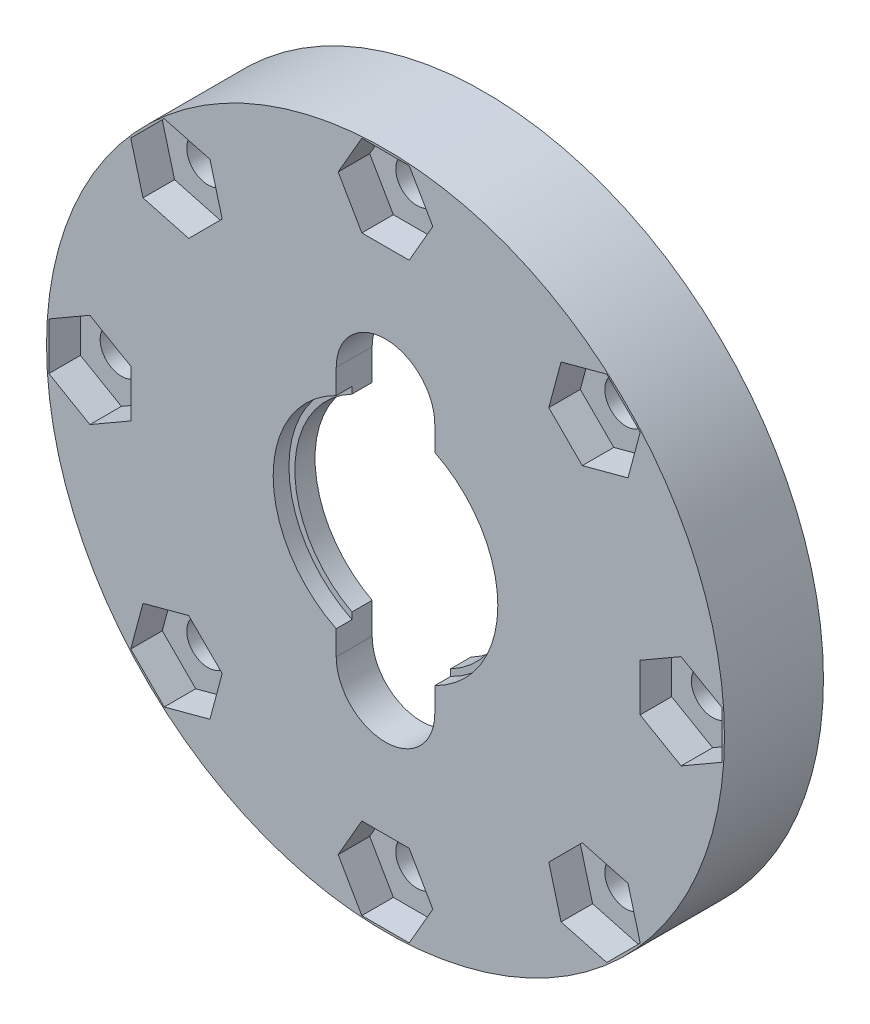
SolidWorks part; units mm, degrees
ref_plane "Front Plane" through (0, 0, 0) normal (0, 0, 1) x (1, 0, 0)
ref_plane "Top Plane" through (0, 0, 0) normal (0, 1, 0) x (1, 0, 0)
ref_plane "Right Plane" through (0, 0, 0) normal (1, 0, 0) x (0, 0, -1)
ref_axis "Z" through (0, 0, -6.594) along (0, 0, 1)
sketch "Sketch3" plane through (0, 0, 0) normal (0, 0, 1) x (1, 0, 0)
  line L0 (-3.125, -6.4031) -> (-3.125, -7.9497)
  line L1 (-3.125, -7.9497) -> (3.125, -7.9497)
  line L2 (3.125, -7.9497) -> (3.125, -6.4031)
  line L3 (3.125, 6.4031) -> (3.125, 7.9494)
  line L4 (3.125, 7.9494) -> (-3.125, 7.9494)
  line L5 (-3.125, 7.9494) -> (-3.125, 6.4031)
  line L132 (3.05, 6.3548) -> (3.05, 6.3561) construction
  line L133 (-3.05, 6.3561) -> (-3.05, 6.3548) construction
  line L134 (3.05, -6.3561) -> (3.05, -6.355) construction
  line L135 (-3.05, -6.355) -> (-3.05, -6.3561) construction
  line L198 (3.05, 6.3548) -> (3.05, 7.8744)
  line L199 (3.05, 7.8744) -> (-3.05, 7.8744)
  line L200 (-3.05, 7.8744) -> (-3.05, 6.3548)
  line L201 (-3.05, 6.3548) -> (-3.4914, 6.1247)
  line L202 (-3.4914, 6.1247) -> (-3.9416, 5.8451)
  line L203 (-3.9416, 5.8451) -> (-4.3696, 5.5325)
  line L204 (-4.3696, 5.5325) -> (-4.7729, 5.1886)
  line L205 (-4.7729, 5.1886) -> (-5.1492, 4.8154)
  line L206 (-5.1492, 4.8154) -> (-5.4964, 4.4149)
  line L207 (-5.4964, 4.4149) -> (-5.8125, 3.9896)
  line L208 (-5.8125, 3.9896) -> (-6.0958, 3.5417)
  line L209 (-6.0958, 3.5417) -> (-6.3446, 3.0737)
  line L210 (-6.3446, 3.0737) -> (-6.5576, 2.5884)
  line L211 (-6.5576, 2.5884) -> (-6.7335, 2.0885)
  line L212 (-6.7335, 2.0885) -> (-6.8714, 1.5768)
  line L213 (-6.8714, 1.5768) -> (-6.9705, 1.0561)
  line L214 (-6.9705, 1.0561) -> (-7.0301, 0.5295)
  line L215 (-7.0301, 0.5295) -> (-7.05, -0.0001)
  line L216 (-7.05, -0.0001) -> (-7.0301, -0.5297)
  line L217 (-7.0301, -0.5297) -> (-6.9705, -1.0563)
  line L218 (-6.9705, -1.0563) -> (-6.8714, -1.577)
  line L219 (-6.8714, -1.577) -> (-6.7335, -2.0887)
  line L220 (-6.7335, -2.0887) -> (-6.5576, -2.5887)
  line L221 (-6.5576, -2.5887) -> (-6.3446, -3.074)
  line L222 (-6.3446, -3.074) -> (-6.0958, -3.5419)
  line L223 (-6.0958, -3.5419) -> (-5.8125, -3.9898)
  line L224 (-5.8125, -3.9898) -> (-5.4964, -4.4152)
  line L225 (-5.4964, -4.4152) -> (-5.1492, -4.8156)
  line L226 (-5.1492, -4.8156) -> (-4.7729, -5.1888)
  line L227 (-4.7729, -5.1888) -> (-4.3696, -5.5327)
  line L228 (-4.3696, -5.5327) -> (-3.9416, -5.8453)
  line L229 (-3.9416, -5.8453) -> (-3.4914, -6.1249)
  line L230 (-3.4914, -6.1249) -> (-3.05, -6.355)
  line L231 (-3.05, -6.355) -> (-3.05, -7.8747)
  line L232 (-3.05, -7.8747) -> (3.05, -7.8747)
  line L233 (3.05, -7.8747) -> (3.05, -6.355)
  line L234 (3.05, -6.355) -> (3.4914, -6.1249)
  line L235 (3.4914, -6.1249) -> (3.9417, -5.8453)
  line L236 (3.9417, -5.8453) -> (4.3696, -5.5327)
  line L237 (4.3696, -5.5327) -> (4.7729, -5.1888)
  line L238 (4.7729, -5.1888) -> (5.1492, -4.8156)
  line L239 (5.1492, -4.8156) -> (5.4964, -4.4152)
  line L240 (5.4964, -4.4152) -> (5.8125, -3.9898)
  line L241 (5.8125, -3.9898) -> (6.0958, -3.5419)
  line L242 (6.0958, -3.5419) -> (6.3447, -3.074)
  line L243 (6.3447, -3.074) -> (6.5576, -2.5887)
  line L244 (6.5576, -2.5887) -> (6.7336, -2.0887)
  line L245 (6.7336, -2.0887) -> (6.8714, -1.577)
  line L246 (6.8714, -1.577) -> (6.9705, -1.0563)
  line L247 (6.9705, -1.0563) -> (7.0301, -0.5297)
  line L248 (7.0301, -0.5297) -> (7.05, -0.0001)
  line L249 (7.05, -0.0001) -> (7.0301, 0.5295)
  line L250 (7.0301, 0.5295) -> (6.9705, 1.0561)
  line L251 (6.9705, 1.0561) -> (6.8714, 1.5768)
  line L252 (6.8714, 1.5768) -> (6.7336, 2.0885)
  line L253 (6.7336, 2.0885) -> (6.5576, 2.5884)
  line L254 (6.5576, 2.5884) -> (6.3447, 3.0737)
  line L255 (6.3447, 3.0737) -> (6.0958, 3.5417)
  line L256 (6.0958, 3.5417) -> (5.8125, 3.9896)
  line L257 (5.8125, 3.9896) -> (5.4964, 4.4149)
  line L258 (5.4964, 4.4149) -> (5.1492, 4.8154)
  line L259 (5.1492, 4.8154) -> (4.7729, 5.1886)
  line L260 (4.7729, 5.1886) -> (4.3696, 5.5325)
  line L261 (4.3696, 5.5325) -> (3.9417, 5.8451)
  line L262 (3.9417, 5.8451) -> (3.4914, 6.1247)
  line L263 (3.4914, 6.1247) -> (3.05, 6.3548)
  line L264 (3.05, 6.3561) -> (3.05, 7.8744) construction
  line L265 (3.05, 7.8744) -> (-3.05, 7.8744) construction
  line L266 (-3.05, 7.8744) -> (-3.05, 6.3561) construction
  line L297 (-3.05, -6.3561) -> (-3.05, -7.8747) construction
  line L298 (-3.05, -7.8747) -> (3.05, -7.8747) construction
  line L299 (3.05, -7.8747) -> (3.05, -6.3561) construction
  arc A1 (-3.05, 6.3561) -> (-3.05, -6.3561) centre (0, 0) ccw construction
  arc A2 (3.05, 6.3561) -> (-3.05, 6.3561) centre (0, 0) ccw construction
  arc A3 (3.05, -6.3561) -> (3.05, 6.3561) centre (0, 0) ccw construction
  arc A4 (-3.05, -6.3561) -> (3.05, -6.3561) centre (0, 0) ccw construction
  circle A5 centre (0, 0) radius 21.5
  arc A6 (-3.125, 6.4031) -> (-3.125, -6.4031) centre (0, 0) ccw
  arc A7 (3.125, -6.4031) -> (3.125, 6.4031) centre (0, 0) ccw
  dimension "D1" = 14.1
  dimension "D3" = 43
  dimension "D2" = 0.075
  dimension "D4" = 0.075
extrude "Boss-Extrude2" add sketch "Sketch3" against normal blind 1
sketch "Sketch4" plane through (0, 0, -1) normal (0, 0, -1) x (-1, 0, 0)
  line L39 (2.75, 6.1644) -> (2.75, 7.5744)
  line L40 (2.75, 7.5744) -> (-2.75, 7.5744)
  line L41 (-2.75, 7.5744) -> (-2.75, 6.1644)
  line L42 (-2.75, -6.1644) -> (-2.75, -7.5747)
  line L43 (-2.75, -7.5747) -> (2.75, -7.5747)
  line L44 (2.75, -7.5747) -> (2.75, -6.1644)
  circle A14 centre (0, 0) radius 21.5
  arc A17 (-2.75, 6.1644) -> (-2.75, -6.1644) centre (0, 0) ccw
  arc A18 (2.75, -6.1644) -> (2.75, 6.1644) centre (0, 0) ccw
  dimension "D1" = 43
extrude "Boss-Extrude3" add sketch "Sketch4" along normal blind 5.28
sketch "Sketch5" plane through (0, 0, -6.28) normal (0, 0, -1) x (-1, 0, 0)
  circle A0 centre (0, 0) radius 17.25
  dimension "D1" = 34.5
extrude "Cut-Extrude1" cut sketch "Sketch5" against normal blind 4
sketch "Sketch6" plane through (0, 0, 0) normal (0, 0, 1) x (1, 0, 0)
  line L0 (0, 0) -> (-18.75, 0) construction
  line L1 (-16.3801, 0) -> (0, 0) construction
  line L3 (-21.35, -1.5011) -> (-18.75, -3.0022)
  line L4 (-18.75, -3.0022) -> (-16.15, -1.5011)
  line L5 (-16.15, -1.5011) -> (-16.15, 1.5011)
  line L6 (-16.15, 1.5011) -> (-18.75, 3.0022)
  line L7 (-18.75, 3.0022) -> (-21.35, 1.5011)
  line L8 (-21.35, 1.5011) -> (-21.35, -1.5011)
  circle A0 centre (-18.75, 0) radius 2.6 construction
  dimension "D1" = 0
  dimension "D2" = 18.75
  dimension "D3" = 5.2
extrude "Cut-Extrude2" cut sketch "Sketch6" against normal blind 2
sketch "Sketch8" plane through (0, 0, 0) normal (0, 0, 1) x (1, 0, 0)
  line L0 (36.6653, 0) -> (49.0214, 0) construction
  line L1 (0, 0) -> (-18.75, 0) construction
  circle A0 centre (0, 0) radius 18.75 construction
  circle A1 centre (-18.75, 0) radius 1.35
  dimension "D1" = 37.5
  dimension "D3" = 2.7
  dimension "D2" = 0
extrude "Cut-Extrude4" cut sketch "Sketch8" against normal through all
pattern_circular "CirPattern1" count 8 over 360 about axis through (0, 0, -6.594) along (0, 0, 1) of "Cut-Extrude2", "Cut-Extrude4"
ref_plane "Plane4" through (0, 0, 0) normal (-0.7071, 0.7071, 0) x (0, 0, 1)
sketch "Sketch9" plane through (0, 0, 0) normal (0, 0, 1) x (1, 0, 0)
  line L1 (-3.125, 7.9494) -> (-3.125, 10.495) construction
  line L2 (0, 0) -> (3.8744, 0) construction
  line L4 (3.125, 7.9494) -> (3.125, -7.9494)
  line L5 (-3.125, 7.9494) -> (-3.125, -7.9494)
  arc A0 (-3.125, 7.9494) -> (3.125, 7.9494) centre (0, 7.9494) cw
  arc A1 (-3.125, -7.9494) -> (3.125, -7.9494) centre (0, -7.9494) ccw
extrude "Cut-Extrude5" cut sketch "Sketch9" against normal through all
equation "\"BearingOD\"= 32"
equation "\"BearingID\" = 25"
equation "\"BearingHeight\"= 4"
equation "\"RetainingRingThickness\" = 1.30"
equation "\"BearingBaseDistance\"= 17.2 - 2*\"BearingHeight\"  - \"RetainingRingThickness\"*2"
equation "\"SeatsOD\"= \"BearingOD\" + 10"
equation "\"WireHarnessHeight\"= 4"
equation "\"OuterWallWidth\"= 6"
equation "\"OverallOD\" = 43"
equation "\"OuterHousingHeight\" = \"WireHarnessHeight\" + \"BearingHeight\"*2 + \"BearingBaseDistance\""
equation "\"RetaininRingGrooveDiameter\" = 23.9"
equation "\"ShaftLengthAfterFlange\" = 2*\"BearingHeight\" + \"BearingBaseDistance\" + \"RetainingRingThickness\"*2\t'give a retaining ring thickness of extra clearance"
equation "\"RetainingRingGrooveBase\" = \"ShaftLengthAfterFlange\" - \"RetainingRingThickness\"*2"
equation "\"CoverThickness\" = 1"
equation "\"CoverClearance\" = 1"
equation "\"FlangHeight\" = 3"
equation "\"PCBWidth\" = 5"
equation "\"PCBHeight\" = \"OuterHousingHeight\" "
equation "\"PCBThickness\" = 1"
equation "\"NormalDistSidewallPCBToZ\" = (\"OverallOD\"/2) - 1.6\t'radial distance from the z axis to pcb origin on the top/connector side"
equation "\"PCBSidewallCutoutClearance\"= 0.1"
equation "\"OutputHubBoltCircleRadius\"= 8"
equation "\"OutputHubOD\"= 27"
equation "\"StatorWireRadius\"= \"NormalDistSidewallPCBToZ\" - 5.7"
equation "\"MountingHoleRadius\"= (\"OverallOD\"+\"BearingOD\")/4"
equation "\"D3@Sketch3\"=\"OverallOD\""
equation "\"D1@Sketch4\"=\"OverallOD\""
equation "\"D1@Sketch8\"=\"MountingHoleRadius\"*2"
equation "\"D2@Sketch6\"=(\"OverallOD\"+\"BearingOD\")/4"
